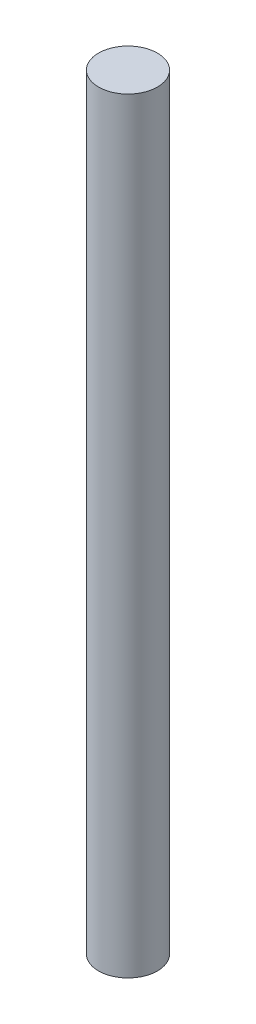
SolidWorks part; units mm, degrees
ref_plane "前视基准面" through (0, 0, 0) normal (0, 0, 1) x (1, 0, 0)
ref_plane "上视基准面" through (0, 0, 0) normal (0, 1, 0) x (1, 0, 0)
ref_plane "右视基准面" through (0, 0, 0) normal (1, 0, 0) x (0, 0, -1)
sketch "草图1" plane through (0, 0, 0) normal (0, 1, 0) x (1, 0, 0)
  circle A0 centre (0, 0) radius 2.5
  dimension "D1" = 5
extrude "凸台-拉伸1" add sketch "草图1" along normal blind 65
